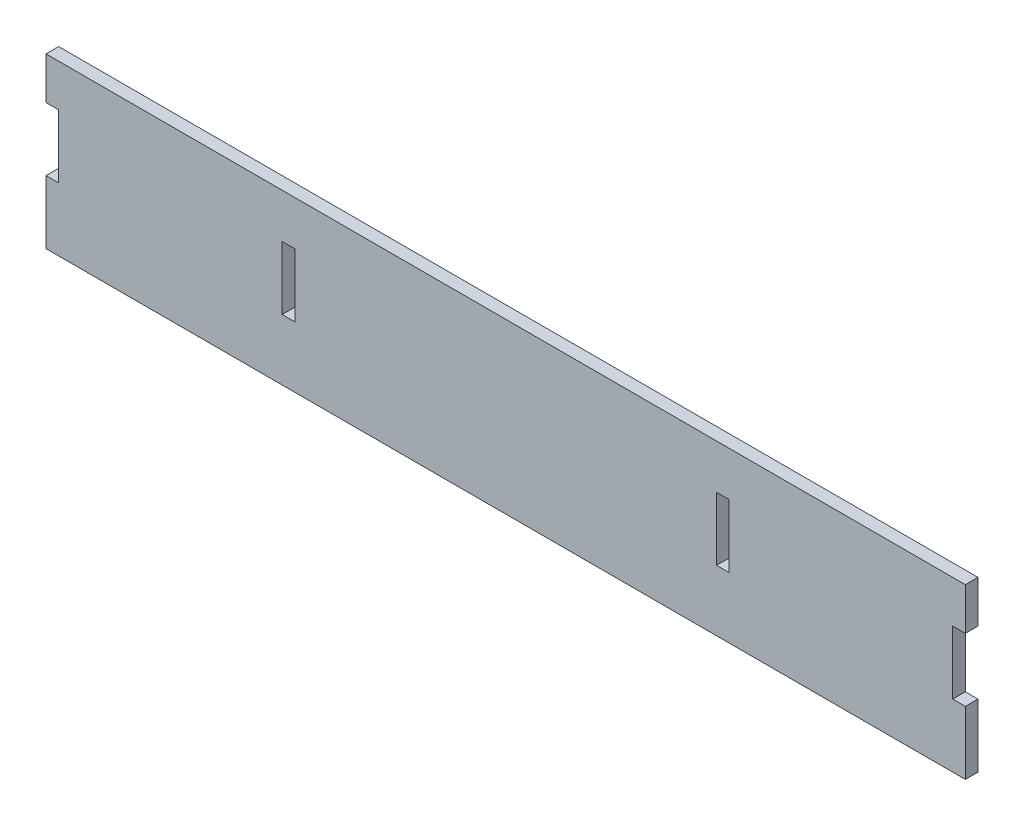
SolidWorks part; units mm, degrees
ref_plane "Front Plane" through (0, 0, 0) normal (0, 0, 1) x (1, 0, 0)
ref_plane "Top Plane" through (0, 0, 0) normal (0, 1, 0) x (1, 0, 0)
ref_plane "Right Plane" through (0, 0, 0) normal (1, 0, 0) x (0, 0, -1)
sketch "Sketch1" plane through (0, 0, 0) normal (0, 0, 1) x (1, 0, 0)
  line L0 (218, 30) -> (218, 40)
  line L1 (0, 0) -> (218, 0)
  line L2 (0, 0) -> (0, 15)
  line L3 (0, 40) -> (218, 40)
  line L4 (218, 0) -> (218, 15)
  line L5 (56, 29.4722) -> (59, 29.4722)
  line L6 (56, 29.4722) -> (56, 14.4722)
  line L7 (56, 14.4722) -> (59, 14.4722)
  line L8 (59, 29.4722) -> (59, 14.4722)
  line L9 (159, 29.4722) -> (162, 29.4722)
  line L10 (159, 29.4722) -> (159, 14.4722)
  line L11 (159, 14.4722) -> (162, 14.4722)
  line L12 (162, 29.4722) -> (162, 14.4722)
  line L13 (0, 30) -> (3, 30)
  line L15 (0, 15) -> (3, 15)
  line L16 (3, 30) -> (3, 15)
  line L17 (218, 30) -> (215, 30)
  line L18 (0, 30) -> (0, 40)
  line L19 (218, 15) -> (215, 15)
  line L20 (215, 30) -> (215, 15)
  dimension "D1" = 3
  dimension "D2" = 15
  dimension "D3" = 218
  dimension "D4" = 15
  dimension "D5" = 3
  dimension "D6" = 56
  dimension "D7" = 100
  dimension "D8" = 56
  dimension "D9" = 40
  dimension "D10" = 10.5278
  dimension "D11" = 10.5278
  dimension "D12" = 10
  dimension "D13" = 10
extrude "Boss-Extrude1" add sketch "Sketch1" along normal blind 3
